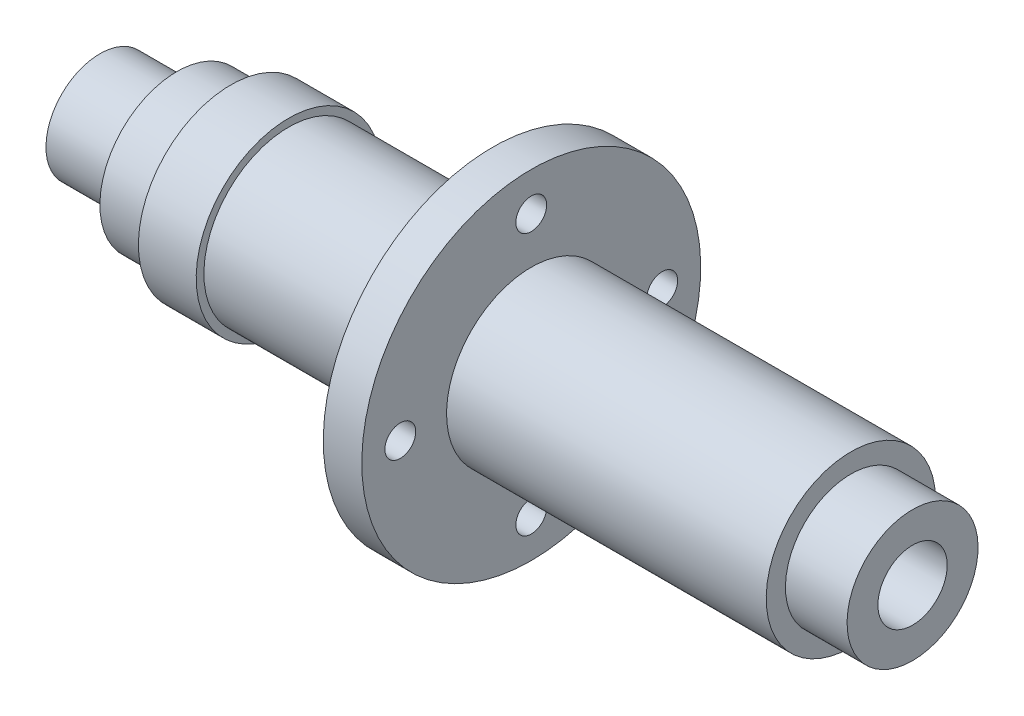
SolidWorks part; units mm, degrees
ref_plane "Front Plane" through (0, 0, 0) normal (0, 0, 1) x (1, 0, 0)
ref_plane "Top Plane" through (0, 0, 0) normal (0, 1, 0) x (1, 0, 0)
ref_plane "Right Plane" through (0, 0, 0) normal (1, 0, 0) x (0, 0, -1)
other "Center of Mass" [suppressed]
sketch "Sketch3" plane through (0, 0, 0) normal (0, 0, 1) x (1, 0, 0)
  line L0 (0, 0) -> (0, 39.0464) construction
  line L1 (-72.5, 0) -> (72.5, 0) construction
  line L2 (-72.5, 2.5) -> (-72.5, 0) construction
  line L3 (-72.5, 2.5) -> (-72.5, 7)
  line L4 (-72.5, 7) -> (-62.5, 7)
  line L5 (-62.5, 7) -> (-62.5, 10)
  line L6 (-62.5, 10) -> (-55.5, 10)
  line L7 (-55.5, 10) -> (-55.5, 12)
  line L8 (-55.5, 12) -> (-38.5, 12)
  line L9 (-38.5, 12) -> (-38.5, 20)
  line L10 (-38.5, 20) -> (-26.5, 20)
  line L11 (-26.5, 20) -> (-26.5, 11)
  line L12 (-26.5, 11) -> (-21.5, 11)
  line L13 (3.5, 11) -> (3.5, 10)
  line L14 (3.5, 10) -> (35.5, 10)
  line L15 (35.5, 10) -> (35.5, 8.5)
  line L17 (72.5, 7.5) -> (72.5, 2.5)
  line L18 (72.5, 2.5) -> (-72.5, 2.5)
  line L19 (-32.5, 20) -> (-32.5, 2.5) construction
  line L20 (-11.5, 11) -> (-11.5, 2.5) construction
  line L21 (-77.5, 12) -> (-72.8417, 12) construction
  line L22 (-62.5, 10) -> (-62.5, 16) construction
  line L23 (-77.5, 15) -> (-72.8417, 15) construction
  line L24 (35.5, 8.5) -> (42.5, 8.5)
  line L25 (11.9511, 11) -> (20.8732, 11) construction
  line L26 (30.861, 12) -> (33.3773, 12) construction
  line L27 (42.5, 8.5) -> (42.5, 7.5)
  line L36 (42.5, 7.5) -> (72.5, 7.5)
  line L37 (-21.5, 11) -> (-21.5, 25)
  line L38 (35.5, 8.5) -> (44.5, 8.5) construction
  line L39 (-21.5, 25) -> (-16.5, 25)
  line L40 (-16.5, 25) -> (-16.5, 11)
  line L42 (-16.5, 11) -> (3.5, 11)
  point P5 (0, 0)
  dimension "D3" = 40
  dimension "D2" = 22
  dimension "D4" = 40
  dimension "D5" = 12
  dimension "D6" = 10
  dimension "D7" = 7
  dimension "D9" = 5
  dimension "D10" = 14
  dimension "D11" = 20
  dimension "D12" = 12
  dimension "D13" = 24
  dimension "D14" = 32
  dimension "D15" = 15
  dimension "D16" = 20
  dimension "D18" = 11
  dimension "D20" = 12
  dimension "D21" = 7
  dimension "D22" = 17
  dimension "D24" = 15
  dimension "D8" = 30
  dimension "D17" = 32
  dimension "D19" = 30
  dimension "D23" = 5
  dimension "D25" = 5
  dimension "D26" = 25
revolve "Revolve1" [suppressed] add sketch "Sketch3" angle 360 about L1
ref_plane "Plane1" [suppressed] through (0, 11, 0) normal (0, 1, 0) x (1, 0, 0)
sketch "Sketch4" [suppressed] plane through (0, 11, 0) normal (0, 1, 0) x (1, 0, 0)
  line L0 (3.5, 0) -> (-26.5, 0) construction
  line L1 (3.5, -11) -> (3.5, 11) construction
  line L2 (-26.5, -11) -> (-26.5, 11) construction
  line L3 (-11.5, 0) -> (-11.5, 23.5234) construction
  line L4 (72.5, -7.5) -> (72.5, 7.5) construction
  line L5 (72.5, 0) -> (62.5, 0) construction
  line L6 (-17.5, -2) -> (-5.5, -2)
  line L7 (-17.5, -2) -> (-17.5, 2)
  line L8 (-17.5, 2) -> (-5.5, 2)
  line L9 (-5.5, -2) -> (-5.5, 2)
  line L10 (-17.5, -2) -> (-5.5, 2) construction
  line L11 (-17.5, 2) -> (-5.5, -2) construction
  line L16 (56.5, -2) -> (68.5, -2)
  line L17 (56.5, -2) -> (56.5, 2)
  line L18 (56.5, 2) -> (68.5, 2)
  line L19 (68.5, -2) -> (68.5, 2)
  line L20 (56.5, -2) -> (68.5, 2) construction
  line L21 (56.5, 2) -> (68.5, -2) construction
  point P17 (62.5, 0)
  dimension "D1" = 12
  dimension "D2" = 4
  dimension "D3" = 10
  dimension "D4" = 12
  dimension "D5" = 4
fillet "Fillet1" [suppressed] radius 1
ref_plane "Plane2" [suppressed] through (0, 7.5, 0) normal (0, 1, 0) x (1, 0, 0)
sketch "Sketch5" [suppressed] plane through (0, 7.5, 0) normal (0, 1, 0) x (1, 0, 0)
  line L0 (68.5, -2) -> (68.5, 2) construction
  line L1 (56.5, -2) -> (68.5, -2) construction
  line L2 (56.5, -2) -> (56.5, 2) construction
  line L3 (56.5, 2) -> (68.5, 2) construction
  line L4 (68.5, -2) -> (68.5, 2)
  line L5 (56.5, -2) -> (68.5, -2)
  line L6 (56.5, -2) -> (56.5, 2)
  line L7 (56.5, 2) -> (68.5, 2)
extrude "Cut-Extrude3" [suppressed] cut sketch "Sketch5" against normal blind 3.2 contours L5 L4 L7 L6
sketch "Sketch6" plane through (0, 0, 0) normal (0, 0, 1) x (1, 0, 0)
  line L0 (-52.75, 0) -> (52.75, 0) construction
  line L1 (-52.75, 4.5) -> (-52.75, 7)
  line L2 (-52.75, 7) -> (-42.75, 7)
  line L3 (-42.75, 7) -> (-42.75, 10)
  line L4 (-42.75, 10) -> (-35.75, 10)
  line L5 (-35.75, 10) -> (-35.75, 12)
  line L6 (-35.75, 12) -> (-28.25, 12)
  line L7 (-28.25, 12) -> (-28.25, 11)
  line L8 (-28.25, 11) -> (-1.75, 11)
  line L9 (44.75, 11) -> (44.75, 8.5)
  line L10 (44.75, 8.5) -> (52.75, 8.5)
  line L11 (52.75, 8.5) -> (52.75, 4.5)
  line L12 (52.75, 4.5) -> (-52.75, 4.5)
  line L13 (8.25, 11) -> (8.25, 4.5) construction
  line L14 (-1.75, 11) -> (-1.75, 22)
  line L15 (-1.75, 22) -> (3.25, 22)
  line L16 (3.25, 22) -> (3.25, 11)
  line L17 (3.25, 11) -> (44.75, 11)
  point P4 (0, 0)
  point P22 (0, 0)
  dimension "D1" = 10
  dimension "D2" = 7
  dimension "D3" = 8
  dimension "D4" = 61
  dimension "D5" = 105.5
  dimension "D6" = 7
  dimension "D7" = 10
  dimension "D8" = 12
  dimension "D9" = 11
  dimension "D10" = 8.5
  dimension "D11" = 9
  dimension "D12" = 31.5
  dimension "D13" = 5
  dimension "D14" = 22
  dimension "D15" = 24.5
revolve "Revolve2" add sketch "Sketch6" angle 360 about L0
ref_plane "Plane3" through (0, 11, 0) normal (0, 1, 0) x (1, 0, 0)
sketch "Sketch8" [suppressed] plane through (-16.5, 0, 0) normal (1, 0, 0) x (0, 0, -1)
  line L0 (0, 0) -> (0, 17) construction
  circle A0 centre (0, 17) radius 2
  circle A1 centre (17, 0) radius 2
  circle A2 centre (0, -17) radius 2
  circle A3 centre (-17, 0) radius 2
  point P12 (0, 0)
  dimension "D1" = 4
  dimension "D3" = 17
  dimension "D4" = 17
  dimension "D5" = 34
  dimension "D2" = 4
extrude "Cut-Extrude5" [suppressed] cut sketch "Sketch8" against normal up to surface (5 mm away)
sketch "Sketch9" plane through (3.25, 0, 0) normal (1, 0, 0) x (0, 0, -1)
  line L0 (0, 0) -> (0, 17) construction
  circle A0 centre (0, 17) radius 2
  circle A1 centre (17, 0) radius 2
  circle A2 centre (0, -17) radius 2
  circle A3 centre (-17, 0) radius 2
  point P12 (0, 0)
  dimension "D1" = 4
  dimension "D2" = 17
  dimension "D4" = 17
  dimension "D5" = 17
  dimension "D3" = 4
extrude "Cut-Extrude6" cut sketch "Sketch9" against normal up to surface (5 mm away) up to face at (-1.75, -11, 0)
equation "\"mainShaft-D\"= 20mm"
equation "\"mainTrackGear-D\"= 40mm"
equation "\"D4@Sketch3\"=\"wormGearL-D\""
equation "\"D11@Sketch3\"=\"mainShaft-D\""
equation "\"mini-flipper-shaft-diameter\"= 26mm"
equation "\"mini-shaft-ring-groove-diam\"= 7.8mm"
equation "\"mini-shaft-ring-groove-width\"= 1mm"
equation "\"dtCoverPlate-DistFrom-GearCent\"= 73mm"
equation "\"wormGearShaft-L\"= \"dtCoverPlate-DistFrom-GearCent\" - 27.75 + 3.75"
equation "\"wormGearShaft-Dsmall\"= 6mm"
equation "\"wormGearShaft-Dworm\"= 12mm"
equation "\"wormL-D\" = 12mm"
equation "\"wormR-D\" = 15mm"
equation "\"wormGearL-D\" = 40mm"
equation "\"wormGearR-D\" = 50mm"
